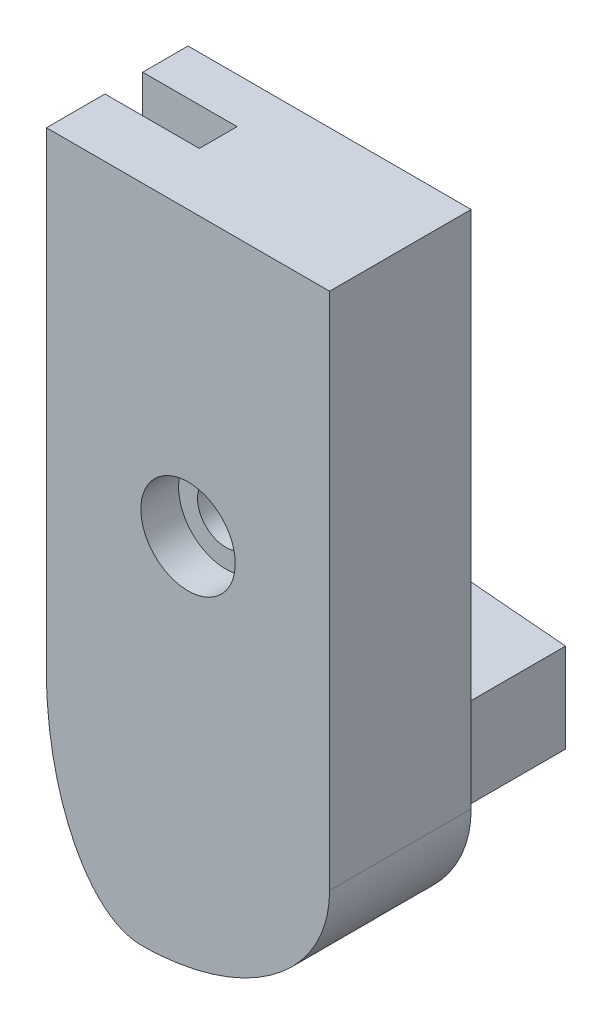
SolidWorks part; units mm, degrees
note: The reader was unsure of these and kept them because the rebuilt part matched: shared geometry of "Sketch7<5>".
ref_plane "Ebene vorne" through (0, 0, 0) normal (0, 0, 1) x (1, 0, 0)
ref_plane "Ebene oben" through (0, 0, 0) normal (0, 1, 0) x (1, 0, 0)
ref_plane "Ebene rechts" through (0, 0, 0) normal (1, 0, 0) x (0, 0, -1)
sketch "Sketch1" plane through (0, 0, 0) normal (0, 0, 1) x (1, 0, 0)
  line L0 (-15, 0) -> (15, 0) construction
  line L1 (-15, 30) -> (15, 30)
  line L2 (-15, 30) -> (-15, -30)
  line L3 (-15, -30) -> (15, -30)
  line L4 (15, 30) -> (15, -30)
  line L5 (0, -30) -> (0, 30) construction
  point P9 (0, 0)
  dimension "D1" = 30
  dimension "D2" = 60
extrude "Boss-Extrude1" add sketch "Sketch1" along normal mid plane 15 contours L1 L4 L3 L2
sketch "Sketch3" plane through (0, 0, 0) normal (1, 0, 0) x (0, 0, -1)
  line L0 (-7.5, -5) -> (-3.5, -5)
  line L1 (-3.5, -5) -> (-3.5, -3)
  line L2 (-3.5, -3) -> (3.5, -3)
  line L3 (3.5, -3) -> (3.5, -5)
  line L4 (3.5, -5) -> (7.5, -5)
  line L5 (-7.5, 30) -> (-7.5, -30) construction
  line L6 (-19.1694, 0) -> (24.4545, 0) construction
  line L7 (-7.5, -5) -> (-7.5, 0)
  line L8 (7.5, -5) -> (7.5, 0)
  line L9 (-7.5, 0) -> (7.5, 0)
  dimension "D1" = 4
  dimension "D2" = 4
  dimension "D3" = 15
  dimension "D4" = 3
  dimension "D5" = 5
revolve "Cut-Revolve1" cut sketch "Sketch3" angle 360 about L6
sketch "Sketch4" plane through (-15, 0, 0) normal (-1, 0, 0) x (0, 0, 1)
  line L0 (7.5, 30) -> (-7.5, 30) construction
  line L1 (-2.6959, 30) -> (1.3041, 30)
  line L2 (-2.6959, 30) -> (-2.6959, -30)
  line L3 (-2.6959, -30) -> (1.3041, -30)
  line L4 (1.3041, 30) -> (1.3041, -30)
  line L5 (7.5, -30) -> (-7.5, -30) construction
  line L6 (-0.6959, 30) -> (-0.6959, -30) construction
  dimension "D1" = 4
extrude "Cut-Extrude1" cut sketch "Sketch4" against normal blind 10
sketch "Sketch5" plane through (0, 0, -7.5) normal (0, 0, 1) x (1, 0, 0)
  line L0 (0, -5.5) -> (-15, -0.0404)
  line L2 (-15, 30) -> (-15, -30) construction
  line L3 (0, -4.0953) -> (-15, 1.3643)
  line L5 (0, -5.5) -> (-15, -5.5) construction
  line L6 (0, -55) -> (0, 55) construction
  line L7 (-15, 1.3643) -> (-15, -0.0404)
  line L8 (0, -4.0953) -> (0, -5.5)
  circle A0 centre (0, 0) radius 5.5 construction
  point P12 (-7.5, -2.7702)
  dimension "D1" = 11
  dimension "D2" = 1.32
  dimension "D3" = 20
extrude "Cut-Extrude2" cut sketch "Sketch5" along normal blind 3
sketch "Sketch6" plane through (0, -30, 0) normal (0, 1, 0) x (1, 0, 0)
  line L1 (-15, 7.5) -> (15, 7.5)
  line L2 (-15, 7.5) -> (-15, -7.5)
  line L3 (-15, -7.5) -> (15, -7.5)
  line L4 (15, -7.5) -> (15, 7.5) construction
  line L5 (-15, 7.5) -> (15, 7.5) construction
  line L6 (-15, -7.5) -> (15, -7.5) construction
  line L7 (15, 7.5) -> (15, -7.5)
extrude "Boss-Extrude2" add sketch "Sketch6" against normal blind 10
fillet "Fillet1" radius 10 1 edges at (-15, -40, 0)
sketch "Sketch7" plane through (0, 0, -7.5) normal (0, 0, -1) x (-1, 0, 0)
  line L0 (0, -30.0686) -> (13.9701, -28.8444)
  line L1 (0, 55) -> (0, -55) construction
  line L2 (0, -40) -> (5, -40)
  line L5 (0, -40) -> (0, -30.0686)
  line L6 (0, -30.0686) -> (0.4135, -29.7387)
  spline S0 degree 2 poles (-167.2056, 945.0607) (-41.5598, -68.9837) (7.889, -39.1472) (9.0837, -38.4263) (10.1542, -37.1387) (11.8677, -35.0778) (13.0536, -31.8557) (14.039, -29.1784) (14.5385, -26.0059) (34.8077, 102.7422) (-835.09, 506.6347) knots -4.248333 -4.248333 -4.248333 0.125 0.125 0.25 0.25 0.5 0.5 0.75 0.75 11.729311 11.729311 11.729311 only from (5, -40) to (15, -20) construction
  spline S1 degree 2 poles (5, -40) (6.4756, -40) (7.889, -39.1472) (9.0837, -38.4263) (10.1542, -37.1387) (11.8677, -35.0778) (13.0536, -31.8557) (13.5816, -30.4212) (13.9701, -28.8444) knots 0 0 0 0.125 0.125 0.25 0.25 0.5 0.5 0.633954 0.633954 0.633954
extrude "Extrude-Thin1" [suppressed] add sketch "Sketch7" along normal blind 20 thin contours L5
extrude "Boss-Extrude3" add sketch "Sketch7<5>" along normal blind 25 contours L0 S1 L2 L5
sketch "Sketch7<5>" plane through (0, 0, -7.5) normal (0, 0, -1) x (-1, 0, 0) same geometry as "Sketch7"
fillet "Fillet2" radius 20 1 edges at (15, -40, 0)
fillet "Fillet3" radius 6 1 edges
fillet "Fillet4" radius 6 1 edges
